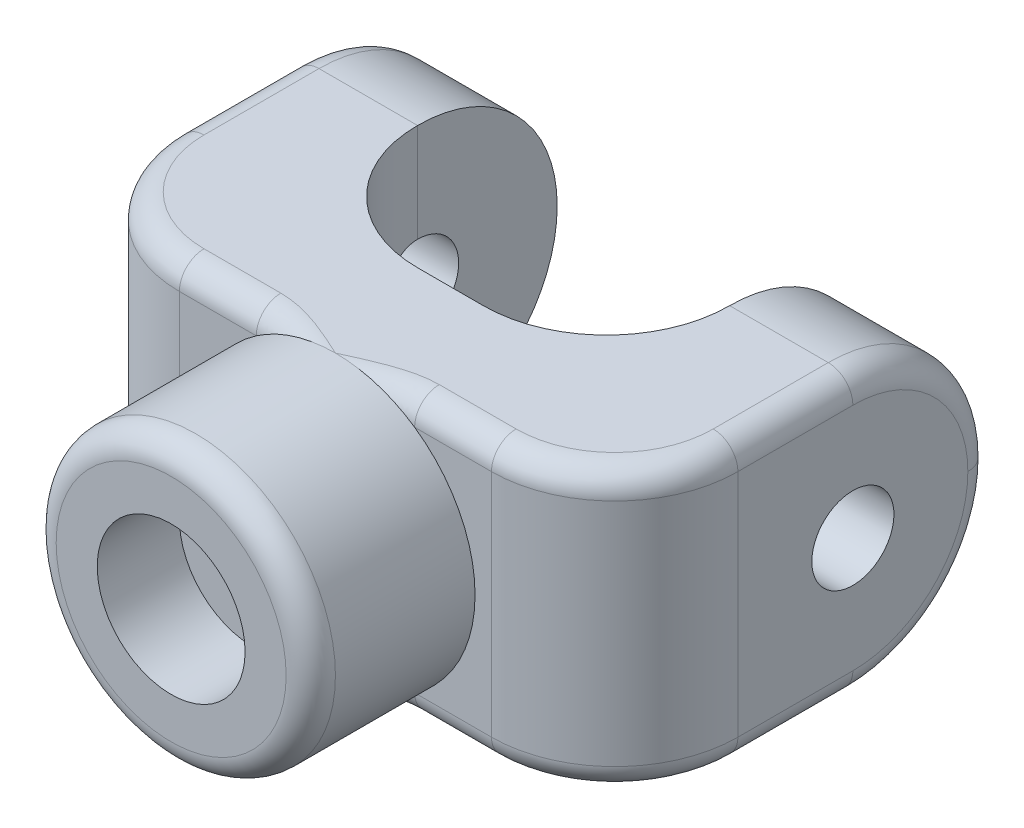
SolidWorks part; units mm, degrees
ref_plane "Front Plane" through (0, 0, 0) normal (0, 0, 1) x (1, 0, 0)
ref_plane "Top Plane" through (0, 0, 0) normal (0, 1, 0) x (1, 0, 0)
ref_plane "Right Plane" through (0, 0, 0) normal (1, 0, 0) x (0, 0, -1)
sketch "Sketch1" plane through (0, 0, 0) normal (0, 1, 0) x (1, 0, 0)
  line L0 (0, 0) -> (0, 14) construction
  line L1 (-34, 0) -> (34, 0)
  line L2 (34, 0) -> (34, 46)
  line L3 (34, 46) -> (19, 46)
  line L4 (19, 46) -> (19, 14)
  line L5 (19, 14) -> (-19, 14)
  line L6 (-19, 46) -> (-19, 14)
  line L7 (-34, 46) -> (-19, 46)
  line L8 (-34, 0) -> (-34, 46)
  dimension "D1" = 14
  dimension "D2" = 34
  dimension "D3" = 46
  dimension "D4" = 15
extrude "Boss-Extrude1" add sketch "Sketch1" along normal mid plane 34
fillet "Fillet1" radius 17 4 edges at (-26.5, 17, -46) (-26.5, -17, -46) (26.5, -17, -46) (26.5, 17, -46)
sketch "Sketch2" plane through (0, 0, 0) normal (0, 0, 1) x (1, 0, 0)
  circle A0 centre (0, 0) radius 17
  dimension "D1" = 34
extrude "Boss-Extrude2" add sketch "Sketch2" along normal blind 20
fillet "Fillet2" radius 3 1 edges at (17, 0, 20)
fillet "Fillet3" radius 15 4 edges at (19, 0, -14) (-19, 0, -14) (-34, 0, 0) (34, 0, 0)
fillet "Fillet4" radius 3 16 edges at (-34, 12.0208, -41.0208) (-34, -12.0208, -41.0208) (-34, -17, -22) (-29.6066, -17, -4.3934) (-9.5, -17, 0) (9.5, -17, 0) (29.6066, -17, -4.3934) (34, -17, -22) (34, -12.0208, -41.0208) (34, 12.0208, -41.0208) (34, 17, -22) (29.6066, 17, -4.3934) (9.5, 17, 0) (-9.5, 17, 0) (-29.6066, 17, -4.3934) (-34, 17, -22)
sketch "Sketch3" plane through (0, 0, 20) normal (0, 0, 1) x (1, 0, 0)
  circle A0 centre (0, 0) radius 9
  dimension "D1" = 18
extrude "Cut-Extrude1" cut sketch "Sketch3" against normal blind 10
sketch "Sketch4" plane through (34, 0, 0) normal (1, 0, 0) x (0, 0, -1)
  circle A0 centre (29, 0) radius 5
  dimension "D1" = 10
extrude "Cut-Extrude2" cut sketch "Sketch4" against normal through all both and the other way through all
